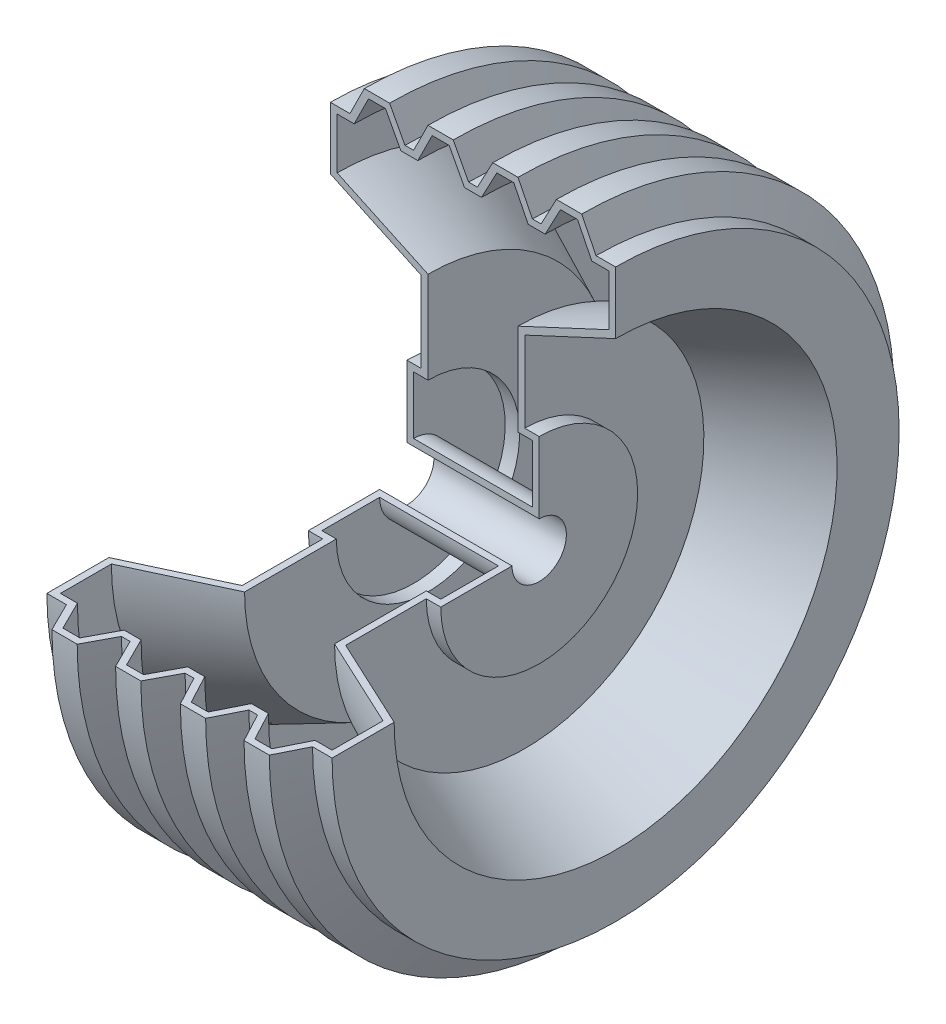
SolidWorks part; units mm, degrees
note: The reader was unsure of these and kept them because the rebuilt part matched: shared geometry of "Sketch1<2>".
ref_plane "Front Plane" through (0, 0, 0) normal (0, 0, 1) x (1, 0, 0)
ref_plane "Top Plane" through (0, 0, 0) normal (0, 1, 0) x (1, 0, 0)
ref_plane "Right Plane" through (0, 0, 0) normal (1, 0, 0) x (0, 0, -1)
sketch "Sketch1" plane through (0, 0, 0) normal (0, 0, 1) x (1, 0, 0)
  line L0 (0, 0) -> (44496.8417, 0) construction
  line L1 (0, 0) -> (0, 44496.8417) construction
  line L2 (-35, 20) -> (35, 20)
  line L3 (35, 20) -> (35, 54)
  line L4 (35, 54) -> (26.5, 54)
  line L5 (26.5, 54) -> (26.5, 108.0525)
  line L6 (26.5, 108.0525) -> (80, 133)
  line L7 (80, 133) -> (80, 163)
  line L8 (80, 163) -> (70, 163)
  line L9 (70, 163) -> (61.5391, 180)
  line L10 (61.5391, 180) -> (51.5391, 180)
  line L11 (51.5391, 180) -> (42.5, 163)
  line L12 (42.5, 163) -> (32.5, 163)
  line L13 (32.5, 163) -> (24.0391, 180)
  line L14 (24.0391, 180) -> (14.0391, 180)
  line L15 (14.0391, 180) -> (5, 163)
  line L16 (5, 163) -> (-5, 163)
  line L17 (-14.0391, 180) -> (-5, 163)
  line L18 (-24.0391, 180) -> (-14.0391, 180)
  line L19 (-32.5, 163) -> (-24.0391, 180)
  line L20 (-42.5, 163) -> (-32.5, 163)
  line L21 (-51.5391, 180) -> (-42.5, 163)
  line L22 (-61.5391, 180) -> (-51.5391, 180)
  line L23 (-70, 163) -> (-61.5391, 180)
  line L24 (-80, 163) -> (-70, 163)
  line L25 (-80, 133) -> (-80, 163)
  line L26 (-26.5, 108.0525) -> (-80, 133)
  line L27 (-26.5, 54) -> (-26.5, 108.0525)
  line L28 (-35, 54) -> (-26.5, 54)
  line L29 (-35, 20) -> (-35, 54)
  point P5 (35, 37)
  point P24 (0, 163)
  point P37 (0, 20)
  dimension "D1" = 17
  dimension "D2" = 30
  dimension "D3" = 40
  dimension "D4" = 360
  dimension "D5" = 108
  dimension "D6" = 10
  dimension "D7" = 62
  dimension "D8" = 160
  dimension "D9" = 65
  dimension "D10" = 53
  dimension "D11" = 70
revolve "Revolve1" [suppressed] add sketch "Sketch1" angle 270 about L0
revolve "Revolve-Thin1" add sketch "Sketch1<2>" angle 270 about L0
sketch "Sketch1<2>" plane through (0, 0, 0) normal (0, 0, 1) x (1, 0, 0) same geometry as "Sketch1"
